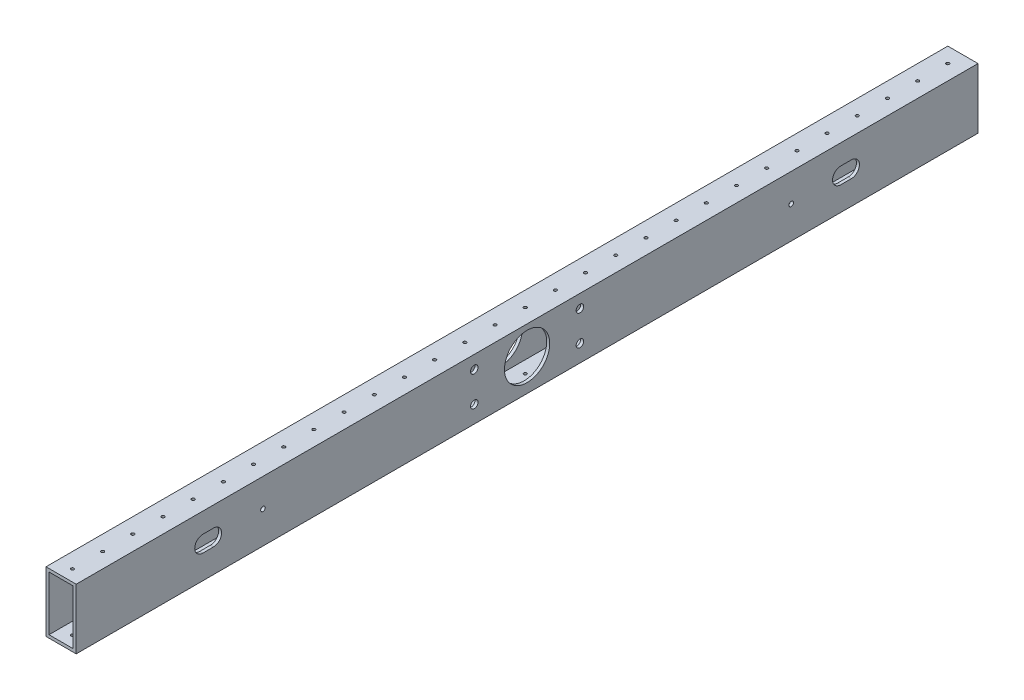
SolidWorks part; units mm, degrees
material "1060 Alloy"
ref_plane "Front Plane" through (0, 0, 0) normal (0, 0, 1) x (1, 0, 0)
ref_plane "Top Plane" through (0, 0, 0) normal (0, 1, 0) x (1, 0, 0)
ref_plane "Right Plane" through (0, 0, 0) normal (1, 0, 0) x (0, 0, -1)
sketch "Sketch1" plane through (0, 0, 0) normal (0, 0, 1) x (1, 0, 0)
  line L1 (-12.7, -25.4) -> (12.7, -25.4)
  line L2 (-12.7, -25.4) -> (-12.7, 25.4)
  line L3 (-12.7, 25.4) -> (12.7, 25.4)
  line L4 (12.7, -25.4) -> (12.7, 25.4)
  point P5 (-12.7, 0)
  point P7 (0, 25.4)
  dimension "D1" = 50.8
  dimension "D2" = 25.4
extrude "Extrude-Thin1" add sketch "Sketch1" along normal mid plane 758.825 thin thin type one direction reverse wall 2.54
sketch "Sketch2" plane through (0, 25.4, 0) normal (0, 1, 0) x (1, 0, 0)
  line L0 (12.7, 379.4125) -> (-12.7, 379.4125) construction
  circle A0 centre (0, 366.7125) radius 1.27
  point P5 (0, 379.4125)
  dimension "D1" = 2.54
  dimension "D2" = 12.7
extrude "Cut-Extrude1" cut sketch "Sketch2" against normal through all
pattern_linear "LPattern1" count 30 spacing 25.4 along (0, 0, 1) of "Cut-Extrude1"
sketch "Sketch4" plane through (-12.7, 0, 0) normal (-1, 0, 0) x (0, 0, 1)
  line L0 (263.906, 1.651) -> (272.796, 1.651) construction
  line L1 (263.906, 8.509) -> (272.796, 8.509)
  line L2 (263.906, -5.207) -> (272.796, -5.207)
  line L3 (-263.906, 1.651) -> (-222.25, 1.651) construction
  line L4 (0, 25.4) -> (0, -25.4) construction
  line L5 (379.4125, 25.4) -> (-379.4125, 25.4) construction
  line L6 (379.4125, -25.4) -> (-379.4125, -25.4) construction
  line L9 (-263.906, 1.651) -> (-272.796, 1.651) construction
  line L10 (-263.906, 8.509) -> (-272.796, 8.509)
  line L11 (-263.906, -5.207) -> (-272.796, -5.207)
  circle A3 centre (0, 1.651) radius 19.05
  arc A6 (-263.906, 8.509) -> (-263.906, -5.207) centre (-263.906, 1.651) cw
  arc A7 (-272.796, -5.207) -> (-272.796, 8.509) centre (-272.796, 1.651) cw
  circle A8 centre (-222.25, 1.651) radius 1.9304
  arc A12 (263.906, 8.509) -> (263.906, -5.207) centre (263.906, 1.651) ccw
  arc A13 (272.796, -5.207) -> (272.796, 8.509) centre (272.796, 1.651) ccw
  circle A14 centre (222.25, 1.651) radius 1.9304
  point P3 (268.351, 1.651)
  point P27 (-268.351, 1.651)
  dimension "D1" = 222.25
  dimension "D4" = 38.1
  dimension "D5" = 6.858
  dimension "D7" = 41.656
  dimension "D6" = 3.8608
  dimension "D2" = 1.651
  dimension "D8" = 8.89
extrude "Cut-Extrude2" cut sketch "Sketch4" against normal through all
sketch "Sketch5" plane through (-12.7, 0, 0) normal (-1, 0, 0) x (0, 0, 1)
  line L0 (-44.45, 14.351) -> (44.45, -11.049) construction
  line L1 (0, -17.399) -> (0, 20.701) construction
  circle A0 centre (0, 1.651) radius 19.05 construction
  circle A12 centre (-44.45, 14.351) radius 3.175
  circle A13 centre (-44.45, -11.049) radius 3.175
  circle A14 centre (44.45, 14.351) radius 3.175
  circle A15 centre (44.45, -11.049) radius 3.175
  point P7 (0, 1.651)
  point P12 (0, 1.651)
  dimension "D1" = 25.4
  dimension "D2" = 88.9
  dimension "D3" = 6.35
extrude "Cut-Extrude3" cut sketch "Sketch5" against normal through all
